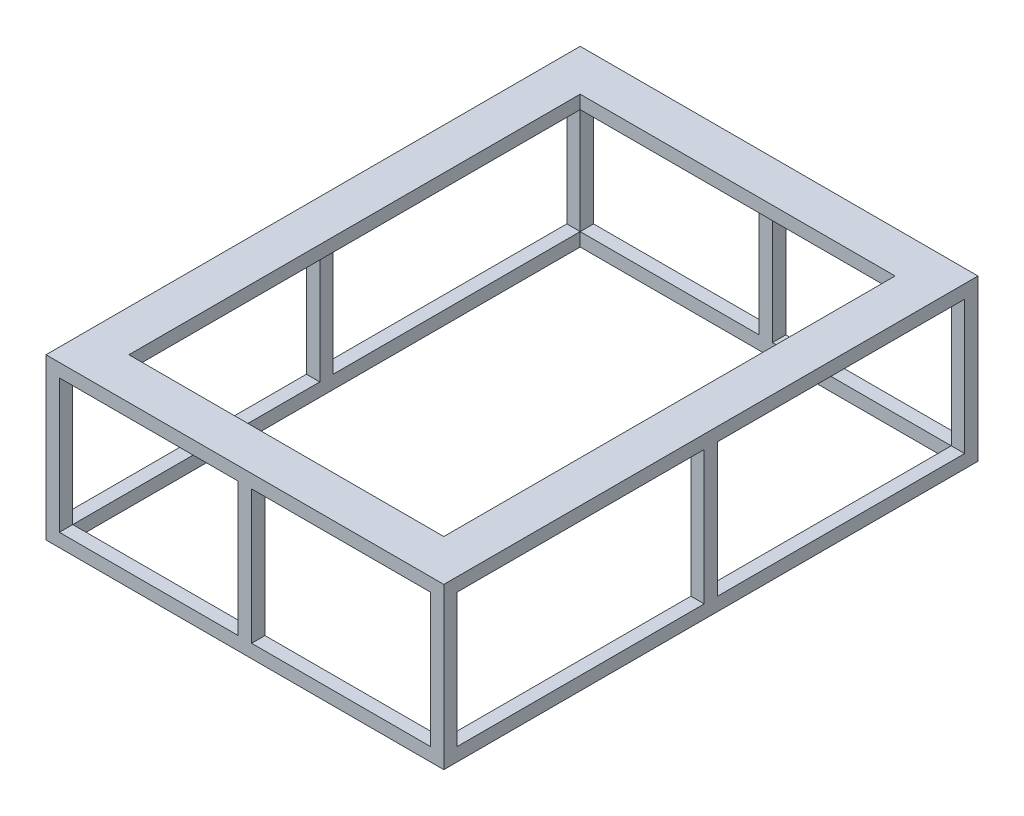
SolidWorks part; units mm, degrees
ref_plane "Front Plane" through (0, 0, 0) normal (0, 0, 1) x (1, 0, 0)
ref_plane "Top Plane" through (0, 0, 0) normal (0, 1, 0) x (1, 0, 0)
ref_plane "Right Plane" through (0, 0, 0) normal (1, 0, 0) x (0, 0, -1)
sketch "Sketch1" plane through (0, 0, 0) normal (0, 1, 0) x (1, 0, 0)
  line L1 (0, 0) -> (253.5, 0)
  line L2 (0, 0) -> (0, 355.5)
  line L3 (0, 355.5) -> (253.5, 355.5)
  line L4 (253.5, 0) -> (253.5, 355.5)
  line L5 (-22, 377.5) -> (275.5, 377.5)
  line L6 (-22, 377.5) -> (-22, -22)
  line L7 (-22, -22) -> (275.5, -22)
  line L8 (275.5, 377.5) -> (275.5, -22)
  line L9 (-12, 367.5) -> (265.5, 367.5)
  line L10 (-12, 367.5) -> (-12, -12)
  line L11 (-12, -12) -> (265.5, -12)
  line L12 (265.5, 367.5) -> (265.5, -12)
  dimension "D1" = 253.5
  dimension "D2" = 355.5
  dimension "D3" = 22
  dimension "D4" = 22
  dimension "D5" = 22
  dimension "D6" = 22
  dimension "D7" = 10
  dimension "D8" = 10
  dimension "D9" = 10
  dimension "D10" = 10
extrude "Boss-Extrude1" add sketch "Sketch1" along normal blind 10 contours L8 L5 L6 L7 L9 L12 L11 L10 region at (126.75, 0, -372.519)
sketch "Sketch2" plane through (0, 10, 0) normal (0, 1, 0) x (1, 0, 0)
  line L0 (-22, -22) -> (275.5, -22) construction
  line L1 (131.75, -22) -> (121.75, -22)
  line L2 (131.75, -22) -> (131.75, -12)
  line L3 (131.75, -12) -> (121.75, -12)
  line L4 (121.75, -22) -> (121.75, -12)
  line L5 (-12, -12) -> (265.5, -12) construction
  line L6 (-12, 367.5) -> (265.5, 367.5) construction
  line L7 (275.5, -22) -> (265.5, -22)
  line L8 (275.5, -22) -> (275.5, -12)
  line L9 (275.5, -12) -> (265.5, -12)
  line L10 (265.5, -22) -> (265.5, -12)
  line L11 (-22, -22) -> (-12, -22)
  line L12 (-22, -22) -> (-22, -12)
  line L13 (-22, -12) -> (-12, -12)
  line L14 (-12, -22) -> (-12, -12)
  line L15 (-22, 377.5) -> (-12, 377.5)
  line L16 (-22, 377.5) -> (-22, 367.5)
  line L17 (-22, 367.5) -> (-12, 367.5)
  line L18 (-12, 377.5) -> (-12, 367.5)
  line L19 (275.5, 377.5) -> (265.5, 377.5)
  line L20 (275.5, 377.5) -> (275.5, 367.5)
  line L21 (275.5, 367.5) -> (265.5, 367.5)
  line L22 (265.5, 377.5) -> (265.5, 367.5)
  line L23 (131.75, 367.5) -> (121.75, 367.5)
  line L24 (131.75, 367.5) -> (131.75, 377.5)
  line L25 (131.75, 377.5) -> (121.75, 377.5)
  line L26 (121.75, 367.5) -> (121.75, 377.5)
  line L27 (-22, 377.5) -> (275.5, 377.5) construction
  line L28 (275.5, 377.5) -> (275.5, -22) construction
  line L29 (275.5, 172.75) -> (265.5, 172.75)
  line L30 (275.5, 172.75) -> (275.5, 182.75)
  line L31 (275.5, 182.75) -> (265.5, 182.75)
  line L32 (265.5, 172.75) -> (265.5, 182.75)
  line L33 (265.5, 367.5) -> (265.5, -12) construction
  line L34 (-12, 367.5) -> (-12, -12) construction
  line L35 (-12, 172.75) -> (-22, 172.75)
  line L36 (-12, 172.75) -> (-12, 182.75)
  line L37 (-12, 182.75) -> (-22, 182.75)
  line L38 (-22, 172.75) -> (-22, 182.75)
  line L39 (-22, 377.5) -> (-22, -22) construction
  dimension "D1" = 133.75
  dimension "D2" = 10
  dimension "D3" = 133.75
  dimension "D4" = 10
  dimension "D5" = 133.75
  dimension "D6" = 10
  dimension "D7" = 184.75
  dimension "D8" = 184.75
  dimension "D9" = 10
  dimension "D10" = 184.75
extrude "Boss-Extrude2" add sketch "Sketch2" along normal blind 100
sketch "Sketch3" plane through (0, 110, 0) normal (0, 1, 0) x (1, 0, 0)
  line L1 (-22, 377.5) -> (275.5, 377.5)
  line L2 (-22, 377.5) -> (-22, -22)
  line L3 (-22, -22) -> (275.5, -22)
  line L4 (275.5, 377.5) -> (275.5, -22)
  line L9 (244.5, 346.5) -> (9, 346.5)
  line L10 (244.5, 346.5) -> (244.5, 9)
  line L11 (244.5, 9) -> (9, 9)
  line L12 (9, 346.5) -> (9, 9)
  dimension "D1" = 235.5
  dimension "D2" = 337.5
  dimension "D3" = 31
  dimension "D4" = 31
  dimension "D5" = 31
  dimension "D6" = 31
extrude "Boss-Extrude3" add sketch "Sketch3" along normal blind 10
